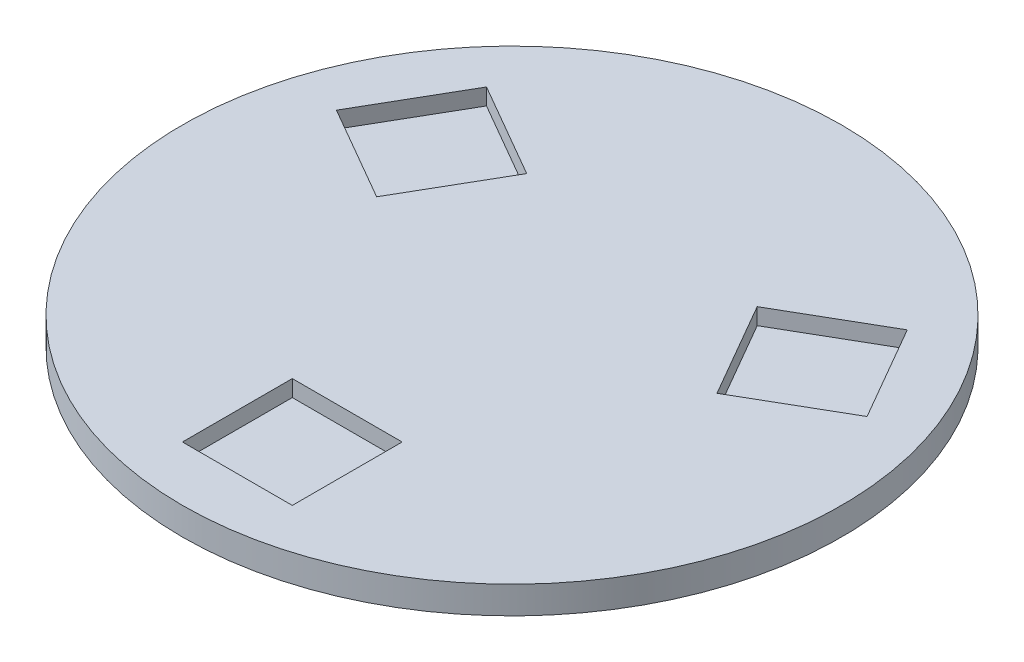
SolidWorks part; units mm, degrees
ref_plane "Front" through (0, 0, 0) normal (0, 0, 1) x (1, 0, 0)
ref_plane "Top" through (0, 0, 0) normal (0, 1, 0) x (1, 0, 0)
ref_plane "Right" through (0, 0, 0) normal (1, 0, 0) x (0, 0, -1)
sketch "Sketch1" plane through (0, 0, 0) normal (0, 1, 0) x (1, 0, 0)
  circle A0 centre (0, 0) radius 3000
extrude "Boss-Extrude1" add sketch "Sketch1" along normal blind 250
sketch "Sketch2" plane through (0, 250, 0) normal (0, 1, 0) x (1, 0, 0)
  line L0 (0, 0) -> (0, -2000) construction
  line L2 (500, -1500) -> (-500, -1500)
  line L3 (500, -1500) -> (500, -2500)
  line L4 (500, -2500) -> (-500, -2500)
  line L5 (-500, -1500) -> (-500, -2500)
  line L6 (500, -1500) -> (-500, -2500) construction
  line L7 (500, -2500) -> (-500, -1500) construction
  dimension "D1" = 2000
  dimension "D2" = 1000
  dimension "D3" = 1000
extrude "Cut-Extrude1" cut sketch "Sketch2" against normal blind 150
pattern_circular "CirPattern1" count 3 over 360 about axis through (0, 250, 0) along (0, 1, 0) of "Cut-Extrude1"
